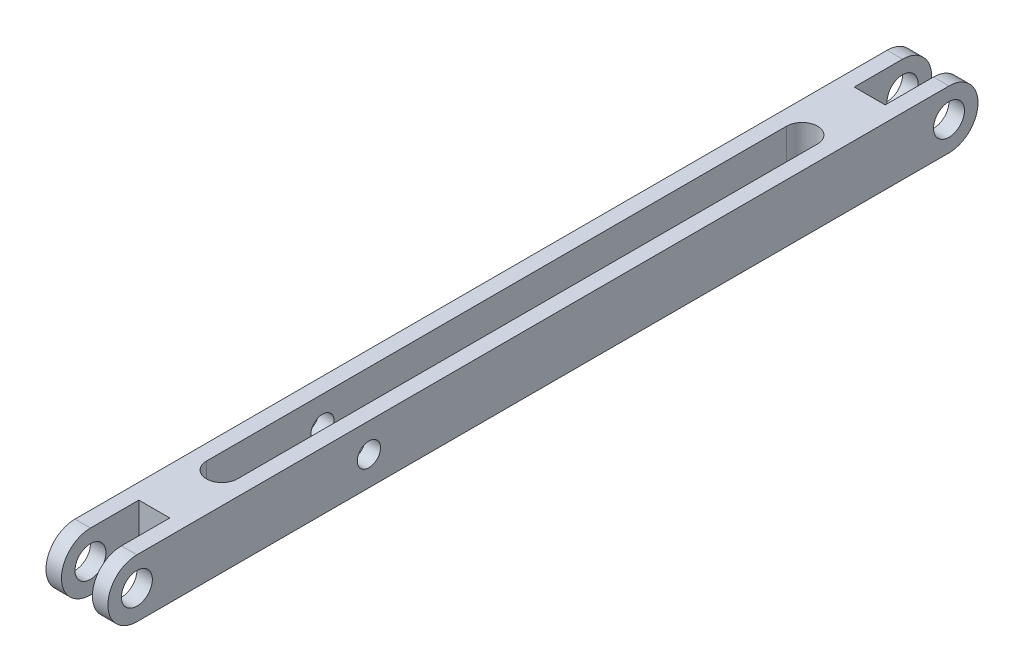
SolidWorks part; units mm, degrees
material "ABS"
ref_plane "前视基准面" through (0, 0, 0) normal (0, 0, 1) x (1, 0, 0)
ref_plane "上视基准面" through (0, 0, 0) normal (0, 1, 0) x (1, 0, 0)
ref_plane "右视基准面" through (0, 0, 0) normal (1, 0, 0) x (0, 0, -1)
sketch "草图2" plane through (0, 0, 0) normal (1, 0, 0) x (0, 0, -1)
  line L0 (-105, 7.5) -> (-105, -7.5) construction
  line L1 (-105, -7.5) -> (105, -7.5)
  line L3 (-105, 7.5) -> (105, 7.5)
  line L5 (-105, -7.5) -> (105, 7.5) construction
  line L6 (-105, 7.5) -> (105, -7.5) construction
  line L7 (105, 7.5) -> (105, -7.5) construction
  arc A0 (-105, 7.5) -> (-105, -7.5) centre (-105, 0) ccw
  arc A1 (105, 7.5) -> (105, -7.5) centre (105, 0) cw
  point P0 (0, 0)
  dimension "D1" = 15
  dimension "D2" = 210
extrude "凸台-拉伸1" add sketch "草图2" along normal blind 16
sketch "草图3" plane through (0, 7.5, 0) normal (0, 1, 0) x (1, 0, 0)
  line L1 (4, -112.5) -> (4, -92.5)
  line L2 (0, -112.5) -> (16, -112.5) construction
  line L3 (4, -92.5) -> (12, -92.5)
  line L4 (12, -92.5) -> (12, -112.5)
  line L5 (12, -112.5) -> (4, -112.5)
  line L6 (0, 105) -> (0, -105) construction
  line L7 (16, 105) -> (16, -105) construction
  line L10 (4, 112.5) -> (12, 112.5)
  line L14 (4, 112.5) -> (4, 92.5)
  line L15 (4, 92.5) -> (12, 92.5)
  line L16 (12, 92.5) -> (12, 112.5)
  line L17 (16, 105) -> (0, 105) construction
  dimension "D1" = 4
  dimension "D2" = 4
  dimension "D3" = 20
  dimension "D4" = 8
  dimension "D5" = 20
  dimension "D6" = 7.5
  dimension "D7" = 4
extrude "切除-拉伸1" cut sketch "草图3" against normal through all
sketch "草图4" plane through (16, 0, 0) normal (1, 0, 0) x (0, 0, -1)
  circle A0 centre (-105, 0) radius 4
  circle A1 centre (105, 0) radius 4
  dimension "D1" = 8
  dimension "D2" = 8
extrude "切除-拉伸2" cut sketch "草图4" against normal through all
sketch "草图5" plane through (0, -7.5, 0) normal (0, -1, 0) x (1, 0, 0)
  line L0 (8, 75) -> (8, -75) construction
  line L1 (12, 75) -> (12, -75)
  line L2 (4, 75) -> (4, -75)
  line L3 (0, 0) -> (8, 0) construction
  line L4 (0, 105) -> (0, -105) construction
  arc A0 (12, 75) -> (4, 75) centre (8, 75) ccw
  arc A1 (4, -75) -> (12, -75) centre (8, -75) ccw
  point P2 (8, 0)
  dimension "D1" = 8
  dimension "D2" = 8
  dimension "D3" = 150
extrude "切除-拉伸3" cut sketch "草图5" against normal through all
sketch "草图6" plane through (0, 0, 0) normal (-1, 0, 0) x (0, 0, 1)
  line L0 (45, 0) -> (0, 0) construction
  circle A1 centre (45, 0) radius 3
  circle A3 centre (105, 0) radius 4 construction
  dimension "D1" = 60
  dimension "D2" = 6
extrude "切除-拉伸4" cut sketch "草图6" against normal through all
